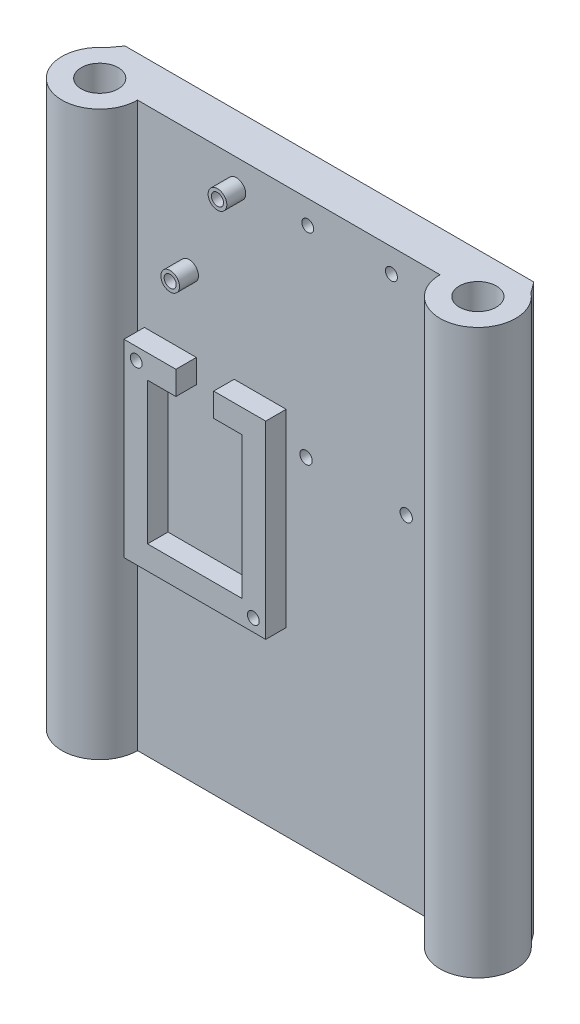
SolidWorks part; units mm, degrees
material "ABS"
ref_plane "Front Plane" through (0, 0, 0) normal (0, 0, 1) x (1, 0, 0)
ref_plane "Top Plane" through (0, 0, 0) normal (0, 1, 0) x (1, 0, 0)
ref_plane "Right Plane" through (0, 0, 0) normal (1, 0, 0) x (0, 0, -1)
sketch "Sketch1" plane through (0, 0, 0) normal (0, 1, 0) x (1, 0, 0)
  line L0 (-50.8, 0) -> (50.8, 0) construction
  line L1 (-40.64, 0) -> (40.64, 0)
  line L2 (-54.8982, 10.9145) -> (54.8982, 10.9145)
  circle A0 centre (-50.8, 0) radius 4.9609
  circle A1 centre (50.8, 0) radius 4.9609
  circle A2 centre (-50.8, 0) radius 10.16
  circle A4 centre (50.8, 0) radius 10.16
  arc A5 (57.0241, 8.0303) -> (-57.0241, 8.0303) centre (0, -31.7761) ccw
  point P4 (0, 0)
  dimension "D1" = 9.9219
  dimension "D2" = 101.6
  dimension "D3" = 20.32
extrude "Boss-Extrude1" add sketch "Sketch1" along normal mid plane 151.384 contours A0 A2 | A4 A1 | A4 A5 L2 A2 L1 region at (0, 0, -5.7083) region at (-55.145, 0, 8.8651) region at (46.455, 0, -8.8651)
sketch "Sketch2" plane through (0, 0, 0) normal (0, 0, 1) x (1, 0, 0)
  line L0 (-23.2789, 0) -> (23.2789, 0) construction
  line L1 (-23.2789, -45.2995) -> (23.2789, -45.2995) construction
  line L2 (-23.2789, -45.2995) -> (-23.2789, 45.2995) construction
  line L3 (-23.2789, 45.2995) -> (23.2789, 45.2995) construction
  line L4 (23.2789, -45.2995) -> (23.2789, 45.2995) construction
  line L5 (-23.2789, -45.2995) -> (23.2789, 45.2995) construction
  line L6 (-23.2789, 45.2995) -> (23.2789, -45.2995) construction
  circle A0 centre (-23.2789, 45.2995) radius 3.175
  circle A1 centre (23.2789, 45.2995) radius 3.175
  circle A2 centre (23.2789, -45.2995) radius 3.175
  circle A3 centre (-23.2789, -45.2995) radius 3.175
  point P0 (0, 0)
  dimension "D1" = 6.35
sketch "Sketch3" plane through (0, 0, 0) normal (0, 0, 1) x (1, 0, 0)
  circle A0 centre (-14.0871, 68.405) radius 1.6256
  circle A1 centre (-26.7871, 43.005) radius 1.6256
  circle A2 centre (-14.0871, 68.405) radius 2.5114
  circle A3 centre (-26.7871, 43.005) radius 2.5114
  dimension "D1" = 3.2512
  dimension "D2" = 12.7
  dimension "D3" = 25.4
extrude "Cut-Extrude1" cut sketch "Sketch3" against normal through all contours A0 | A1
extrude "Boss-Extrude2" add sketch "Sketch3<3>" along normal blind 5.08
sketch "Sketch3<3>" plane through (0, 0, 0) normal (0, 0, 1) x (1, 0, 0) same geometry as "Sketch3"
sketch "Sketch4" plane through (0, 0, 0) normal (0, 0, 1) x (1, 0, 0)
  circle A0 centre (5.0971, 69.338) radius 1.5806
  circle A1 centre (27.5695, 69.3267) radius 1.616
  circle A3 centre (4.6303, 15.1788) radius 1.651
  circle A4 centre (31.5543, 15.1951) radius 1.651
extrude "Cut-Extrude2" cut sketch "Sketch4" against normal through all
sketch "Sketch5" plane through (0, 0, 0) normal (0, 0, 1) x (1, 0, 0)
  line L0 (-24.8378, 17.3607) -> (-24.8378, 23.7107)
  line L1 (-32.4578, -20.7393) -> (-7.0578, -20.7393)
  line L2 (-32.4578, -20.7393) -> (-32.4578, 17.3607)
  line L3 (-32.4578, 17.3607) -> (-7.0578, 17.3607)
  line L4 (-7.0578, -20.7393) -> (-7.0578, 17.3607)
  line L5 (-32.4578, -20.7393) -> (-7.0578, 17.3607) construction
  line L6 (-32.4578, 17.3607) -> (-7.0578, -20.7393) construction
  line L7 (-0.7078, -27.0893) -> (-38.8078, -27.0893)
  line L8 (-0.7078, -27.0893) -> (-0.7078, 23.7107)
  line L9 (-0.7078, 23.7107) -> (-38.8078, 23.7107)
  line L10 (-38.8078, -27.0893) -> (-38.8078, 23.7107)
  line L11 (-0.7078, -27.0893) -> (-38.8078, 23.7107) construction
  line L12 (-0.7078, 23.7107) -> (-38.8078, -27.0893) construction
  line L13 (-14.6778, 17.3607) -> (-14.6778, 23.7107)
  point P0 (-19.7578, -1.6893)
  point P6 (-19.7578, -1.6893)
  point P14 (-19.7578, 17.3607)
  dimension "D1" = 25.4
  dimension "D2" = 38.1
  dimension "D3" = 50.8
  dimension "D4" = 5.08
  dimension "D5" = 5.08
  dimension "D6" = 38.1
extrude "Boss-Extrude3" add sketch "Sketch5" along normal blind 5.5001 contours L13 L3 L4 L1 L2 L0 L9 L10 L7 L8 region at (-28.6478, 17.9957, 0)
sketch "Sketch6" plane through (0, 0, 5.5001) normal (0, 0, 1) x (1, 0, 0)
  line L0 (-35.4829, 23.7107) -> (-35.4829, 20.3858) construction
  line L1 (-24.8378, 23.7107) -> (-38.8078, 23.7107) construction
  line L2 (-38.8078, 20.3858) -> (-35.4829, 20.3858) construction
  line L3 (-38.8078, -27.0893) -> (-38.8078, 23.7107) construction
  line L4 (-0.7078, -23.7644) -> (-4.0327, -23.7644) construction
  line L5 (-0.7078, -27.0893) -> (-0.7078, 23.7107) construction
  line L6 (-4.0327, -23.7644) -> (-4.0327, -27.0893) construction
  line L7 (-0.7078, -27.0893) -> (-38.8078, -27.0893) construction
  circle A0 centre (-35.4829, 20.3858) radius 1.5875
  circle A1 centre (-4.0327, -23.7644) radius 1.5875
  point P2 (0, 0)
  point P5 (0, 0)
  point P16 (-3.641, -23.4517)
  dimension "D1" = 3.175
  dimension "D2" = 3.175
extrude "Cut-Extrude3" cut sketch "Sketch6" against normal through all
